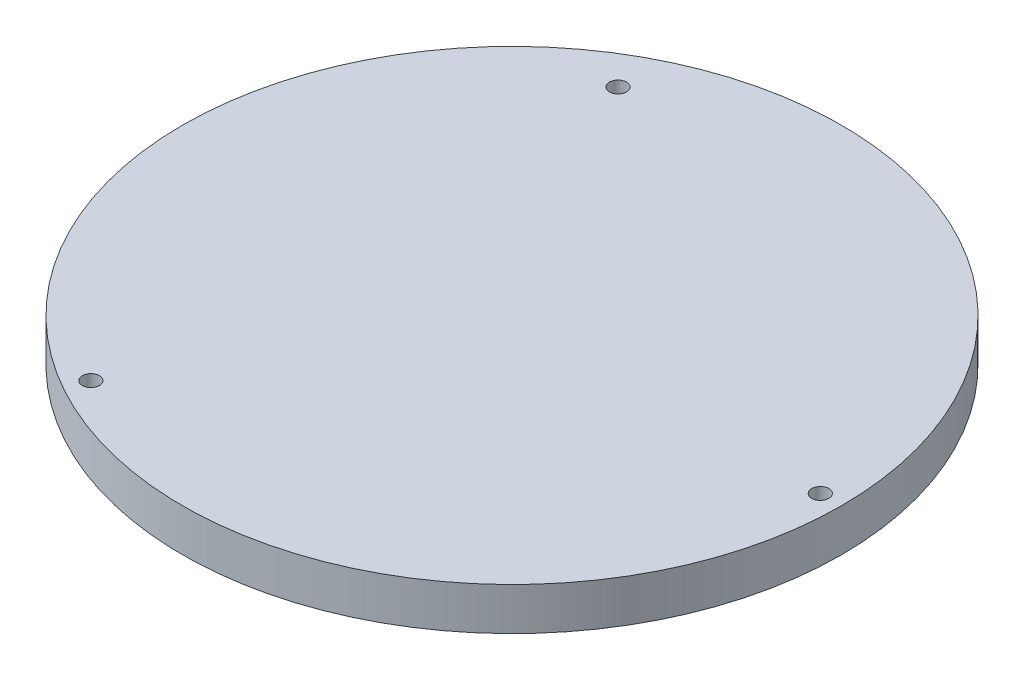
SolidWorks part; units mm, degrees
ref_plane "Front Plane" through (0, 0, 0) normal (0, 0, 1) x (1, 0, 0)
ref_plane "Top Plane" through (0, 0, 0) normal (0, 1, 0) x (1, 0, 0)
ref_plane "Right Plane" through (0, 0, 0) normal (1, 0, 0) x (0, 0, -1)
sketch "Sketch1" plane through (0, 0, 0) normal (0, 0, 1) x (1, 0, 0)
  line L0 (0, -200000) -> (0, 218797.9879) construction
  line L1 (98.425, -26.7494) -> (98.425, -39.4494) construction
  line L2 (0, -26.7494) -> (98.425, -26.7494) construction
  line L3 (98.425, -39.4494) -> (0, -39.4494) construction
  line L4 (0, -200000) -> (0, 218797.9879) construction
  line L5 (98.425, -26.7494) -> (98.425, -39.4494)
  line L6 (0, -26.7494) -> (98.425, -26.7494)
  line L7 (98.425, -39.4494) -> (0, -39.4494)
  line L8 (0, -26.7494) -> (0, -39.4494)
revolve "Revolve1" add sketch "Sketch1" angle 360 about L4
hole_wizard "1/4-20 Tapped Hole1" positions "Sketch2" profile "Sketch3" tap size "1/4-20" standard "ANSI Inch" end condition up to next
sketch "Sketch2" plane through (0, -26.7494, 0) normal (0, 1, 0) x (1, 0, 0)
  line L0 (0, 0) -> (92.075, 0) construction
  line L3 (0, 0) -> (-46.0375, -79.7393) construction
  line L6 (0, 0) -> (-43.2486, 74.9088) construction
  circle A0 centre (0, 0) radius 92.075
  point P0 (92.075, 0)
  point P2 (-46.0375, -79.7393)
  point P4 (-43.2486, 74.9088)
  dimension "D1" = 120
  dimension "D2" = 120
sketch "Sketch3" plane through (92.075, -26.7494, 0) normal (1, 0, 0) x (0, 0, 1)
  line L0 (0, 0) -> (0, 12.7)
  line L1 (0, 12.7) -> (2.5527, 12.7)
  line L2 (2.5527, 12.7) -> (2.5527, 0)
  line L5 (2.5527, 0) -> (0, 0)
  line L11 (0, -6.35) -> (0, 107.95) construction
  dimension "Thru Tap Drill Dia." = 5.1054
  dimension "Thru Tap Drill Depth" = 12.7
cosmetic thread "Hole Thread1" parameters "D2"=6.35
cosmetic thread "Hole Thread2" parameters "D2"=6.35
cosmetic thread "Hole Thread3" parameters "D2"=6.35
